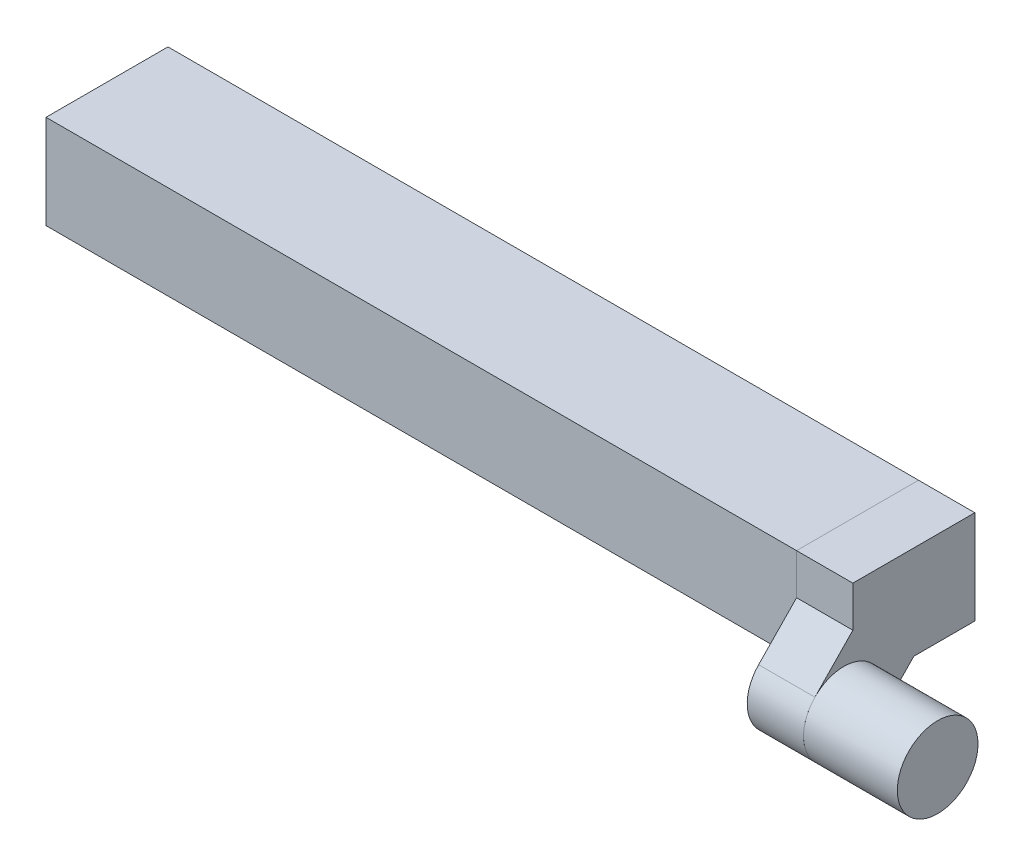
SolidWorks part; units mm, degrees
ref_plane "Front Plane" through (0, 0, 0) normal (0, 0, 1) x (1, 0, 0)
ref_plane "Top Plane" through (0, 0, 0) normal (0, 1, 0) x (1, 0, 0)
ref_plane "Right Plane" through (0, 0, 0) normal (1, 0, 0) x (0, 0, -1)
sketch "Sketch2" plane through (0, 0, 0) normal (1, 0, 0) x (0, 0, -1)
  line L1 (-2.05, -2.05) -> (2.05, -2.05)
  line L2 (-2.05, -2.05) -> (-2.05, 2.05)
  line L3 (-2.05, 2.05) -> (2.05, 2.05)
  line L4 (2.05, -2.05) -> (2.05, 2.05)
  line L5 (-2.05, -2.05) -> (2.05, 2.05) construction
  line L6 (-2.05, 2.05) -> (2.05, -2.05) construction
  line L7 (3.25, -2.5) -> (-3.25, -2.5)
  line L8 (3.25, -2.5) -> (3.25, 2.5)
  line L9 (3.25, 2.5) -> (-3.25, 2.5)
  line L10 (-3.25, -2.5) -> (-3.25, 2.5)
  line L11 (3.25, -2.5) -> (-3.25, 2.5) construction
  line L12 (3.25, 2.5) -> (-3.25, -2.5) construction
  point P0 (0, 0)
  point P5 (0, 0)
  dimension "D1" = 4.1
  dimension "D2" = 4.1
  dimension "D3" = 6.5
  dimension "D4" = 5
extrude "Boss-Extrude1" add sketch "Sketch2" along normal blind 10
extrude "Boss-Extrude2" add sketch "Sketch2<2>" along normal blind 25 from offset 15 contours L1 L4 L3 L2 | L10 L7 L8 L9 L4 L1 L2 L3 region at (0, 0, 0) region at (0, -2.418, 0)
sketch "Sketch2<2>" plane through (0, 0, 0) normal (1, 0, 0) x (0, 0, -1) same geometry as "Sketch2"
sketch "Sketch5" plane through (40, 0, 0) normal (1, 0, 0) x (0, 0, -1)
  line L0 (-0.02, -0.4959) -> (-4.75, -0.4959) construction
  line L6 (-3.25, 2.5) -> (3.25, 2.5)
  line L7 (3.25, 2.5) -> (3.25, -2.5)
  line L8 (3.25, -2.5) -> (0, -2.5)
  line L9 (-3.25, -2.5) -> (3.25, -2.5) construction
  line L10 (0, -2.5) -> (-2.189, -4.7517)
  line L11 (-5.2722, -1.7543) -> (-3.25, 0.3257)
  line L12 (-3.25, -2.5) -> (-3.25, 2.5) construction
  line L13 (-5.2722, -1.7543) -> (-2.189, -4.7517) construction
  line L14 (-3.25, 0.3257) -> (-3.25, 2.5)
  arc A1 (-5.2722, -1.7543) -> (-2.189, -4.7517) centre (-3.7306, -3.253) ccw
  dimension "D1" = 4.73
  dimension "D3" = 5
  dimension "D4" = 4.3
extrude "Boss-Extrude3" add sketch "Sketch5" along normal blind 3
sketch "Sketch6" plane through (43, 0, 0) normal (1, 0, 0) x (0, 0, -1)
  circle A1 centre (-3.7306, -3.253) radius 2.15
  dimension "D1" = 4.3
extrude "Boss-Extrude4" add sketch "Sketch6" along normal blind 5
extrude "Boss-Extrude5" add sketch "Sketch2<4>" along normal blind 5 from offset 10
sketch "Sketch2<4>" plane through (0, 0, 0) normal (1, 0, 0) x (0, 0, -1) same geometry as "Sketch2"
